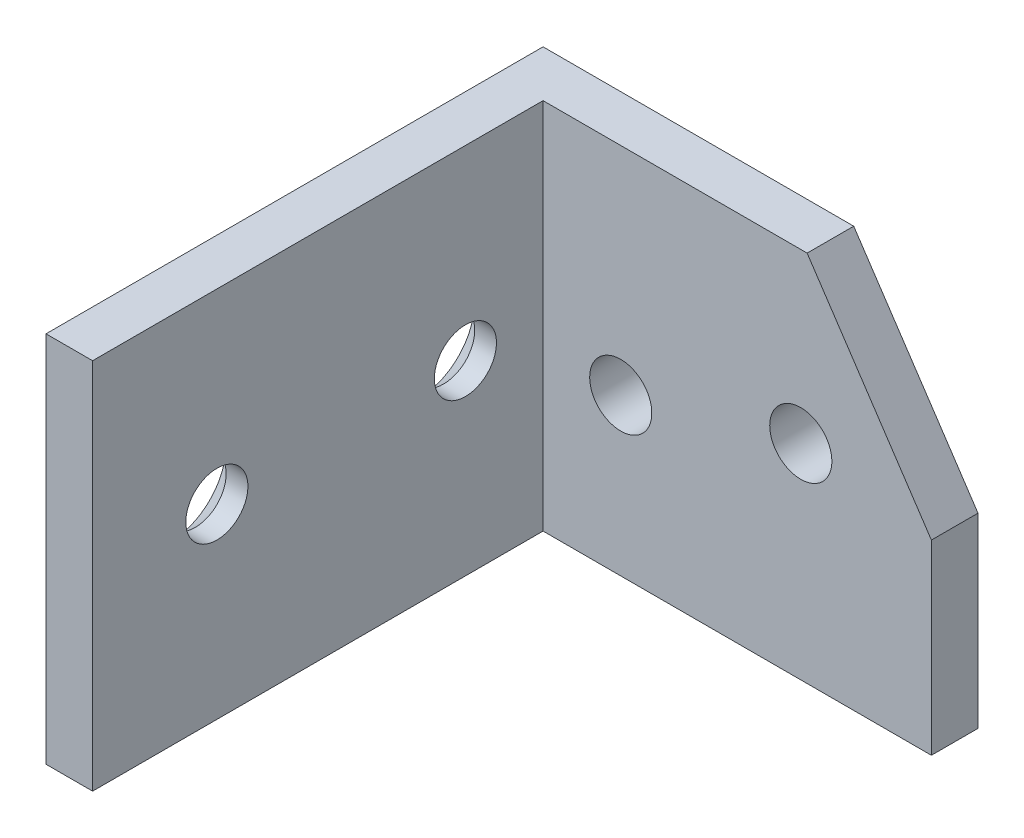
SolidWorks part; units mm, degrees
material "6061 Alloy"
ref_plane "Front Plane" through (0, 0, 0) normal (0, 0, 1) x (1, 0, 0)
ref_plane "Top Plane" through (0, 0, 0) normal (0, 1, 0) x (1, 0, 0)
ref_plane "Right Plane" through (0, 0, 0) normal (1, 0, 0) x (0, 0, -1)
sketch "Sketch1" plane through (0, 0, 0) normal (0, 1, 0) x (1, 0, 0)
  line L0 (0, 0) -> (0, 46.0375)
  line L1 (0, 46.0375) -> (39.6875, 46.0375)
  line L2 (39.6875, 46.0375) -> (39.6875, 50.8)
  line L3 (39.6875, 50.8) -> (-4.7625, 50.8)
  line L4 (-4.7625, 50.8) -> (-4.7625, 0)
  line L5 (-4.7625, 0) -> (0, 0)
  dimension "D1" = 44.45
  dimension "D2" = 50.8
  dimension "D3" = 4.7625
  dimension "D4" = 4.7625
extrude "Boss-Extrude1" add sketch "Sketch1" along normal blind 38.1
sketch "Sketch2" plane through (0, 0, -50.8) normal (0, 0, -1) x (-1, 0, 0)
  line L2 (-39.6875, 24.5038) -> (4.7625, 12.5935) construction
  line L3 (-39.6875, 38.1) -> (-39.6875, 0) construction
  line L4 (4.7625, 38.1) -> (4.7625, 0) construction
  line L5 (-39.6875, 38.1) -> (4.7625, 38.1) construction
  circle A0 centre (-26.3384, 20.9269) radius 3.175
  circle A1 centre (-7.9375, 15.9964) radius 3.175
  dimension "D1" = 6.35
  dimension "D2" = 15
  dimension "D3" = 0
  dimension "D4" = 19.05
  dimension "D7" = 6.35
  dimension "D6" = 12.7
  dimension "D5" = 0
extrude "Cut-Extrude1" cut sketch "Sketch2" against normal blind 38.1
sketch "Sketch3" plane through (-4.7625, 0, 0) normal (-1, 0, 0) x (0, 0, 1)
  line L2 (-50.8, 0) -> (0, 0) construction
  line L3 (0, 38.1) -> (0, 0) construction
  circle A0 centre (-12.7, 19.05) radius 3.175
  circle A1 centre (-38.1, 19.05) radius 3.175
  dimension "D1" = 6.35
  dimension "D2" = 6.35
  dimension "D3" = 19.05
  dimension "D4" = 19.05
  dimension "D5" = 12.7
  dimension "D6" = 25.4
extrude "Cut-Extrude3" cut sketch "Sketch3" against normal up to next
chamfer "Chamfer1" distance 2.54 angle 45 2 edges at (-4.7625, 19.05, -9.525) (-4.7625, 19.05, -34.925)
sketch "Sketch4" plane through (0, 0, -50.8) normal (0, 0, -1) x (-1, 0, 0)
  line L0 (-26.9875, 38.1) -> (-39.6875, 19.05)
  line L3 (-39.6875, 38.1) -> (4.7625, 38.1) construction
  line L4 (-39.6875, 38.1) -> (-39.6875, 0) construction
  dimension "D1" = 12.7
  dimension "D2" = 19.05
extrude "Cut-Extrude4" cut sketch "Sketch4" against normal through all and the other way through all flip side to cut contours L0
